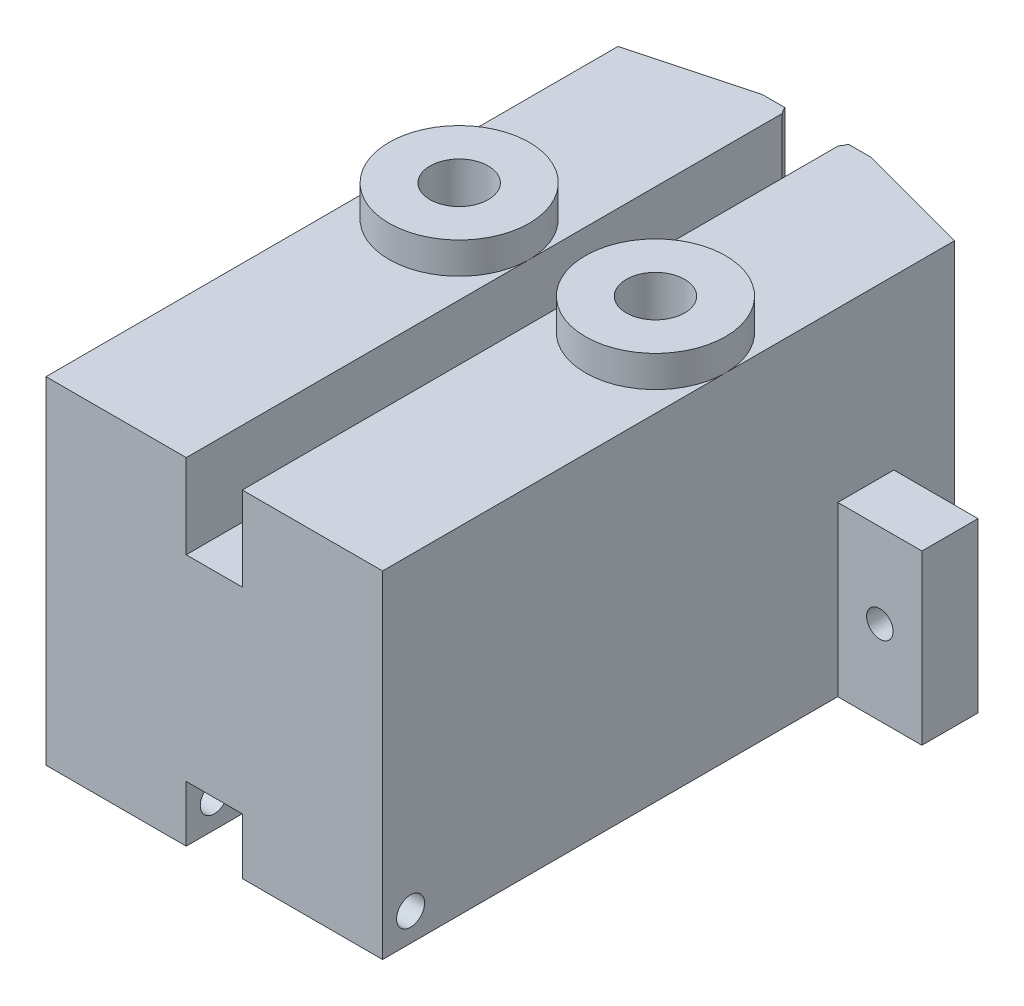
SolidWorks part; units mm, degrees
material "A-Glass Fiber"
ref_plane "Front Plane" through (0, 0, 0) normal (0, 0, 1) x (1, 0, 0)
ref_plane "Top Plane" through (0, 0, 0) normal (0, 1, 0) x (1, 0, 0)
ref_plane "Right Plane" through (0, 0, 0) normal (1, 0, 0) x (0, 0, -1)
sketch "Sketch1" plane through (0, 0, 0) normal (1, 0, 0) x (0, 0, -1)
  line L0 (-19.05, 0) -> (19.05, 0) construction
  line L1 (-19.05, 9.525) -> (19.05, 9.525)
  line L2 (-19.05, 9.525) -> (-19.05, -9.525)
  line L3 (-19.05, -9.525) -> (19.05, -9.525)
  line L4 (19.05, 9.525) -> (19.05, -9.525)
  dimension "D1" = 9.525
  dimension "D2" = 19.05
  dimension "D3" = 38.1
extrude "Boss-Extrude1" add sketch "Sketch1" along normal mid plane 19.05
sketch "Sketch2" plane through (0, 0, 0) normal (0, 1, 0) x (1, 0, 0)
  line L0 (-3.0668, 15.0532) -> (-9.525, 13.3228)
  line L1 (-9.525, 19.05) -> (-9.525, -19.05) construction
  line L2 (3.0668, 15.0532) -> (9.525, 13.3228)
  line L3 (9.525, 19.05) -> (9.525, -19.05) construction
  line L4 (9.525, 19.05) -> (-9.525, 19.05) construction
  arc A0 (-3.0668, 15.0532) -> (3.0668, 15.0532) centre (0, 15.875) cw
  dimension "D1" = 3.175
  dimension "D2" = 15
  dimension "D3" = 15
extrude "Cut-Extrude1" cut sketch "Sketch2" against normal through all both and the other way through all
sketch "Sketch3" plane through (0, 0, 0) normal (0, 1, 0) x (1, 0, 0)
  circle A0 centre (0, 15.875) radius 1.9844
  arc A1 (3.0668, 15.0532) -> (-3.0668, 15.0532) centre (0, 15.875) ccw construction
  dimension "D1" = 3.9688
extrude "Cut-Extrude2" cut sketch "Sketch3" against normal through all both and the other way through all
sketch "Sketch4" plane through (0, 0, 0) normal (0, 0, 1) x (1, 0, 0)
  line L0 (9.525, 9.525) -> (-9.525, 9.525) construction
  line L1 (-1.5875, 9.525) -> (1.5875, 9.525)
  line L2 (-1.5875, 9.525) -> (-1.5875, 4.7625)
  line L3 (-1.5875, 4.7625) -> (1.5875, 4.7625)
  line L4 (1.5875, 9.525) -> (1.5875, 4.7625)
  line L5 (0, -9.525) -> (0, 9.525) construction
  line L6 (9.525, -9.525) -> (-9.525, -9.525) construction
  line L8 (-1.5875, -9.525) -> (1.5875, -9.525)
  line L9 (-1.5875, -9.525) -> (-1.5875, -6.35)
  line L10 (-1.5875, -6.35) -> (1.5875, -6.35)
  line L11 (1.5875, -9.525) -> (1.5875, -6.35)
  dimension "D1" = 4.7625
  dimension "D2" = 3.175
  dimension "D3" = 6.35
extrude "Cut-Extrude3" cut sketch "Sketch4" against normal through all both and the other way through all
sketch "Sketch11" plane through (0, 4.7625, 0) normal (0, 1, 0) x (1, 0, 0)
  circle A0 centre (0, 15.875) radius 3.683
  arc A1 (1.5875, 18.6246) -> (-1.5875, 18.6246) centre (0, 15.875) ccw construction
  dimension "D1" = 0.508
extrude "Cut-Extrude9" cut sketch "Sketch11" against normal offset from surface (6.35 mm away) 2.3813 from offset 2.3813 up to face at (0, -6.35, 2.3813) offset against normal yes
ref_plane "SymmetryPlane" through (0, -0.7937, 0) normal (0, -1, 0) x (-1, 0, 0)
sketch "Sketch12" plane through (0, 0, 0) normal (1, 0, 0) x (0, 0, -1)
  line L0 (18.6246, -6.35) -> (19.05, -6.35) construction
  line L1 (18.6246, -9.525) -> (12.2746, -9.525)
  line L2 (18.6246, -9.525) -> (18.6246, -6.35)
  line L3 (18.6246, -6.35) -> (12.2746, -6.35)
  line L4 (12.2746, -9.525) -> (12.2746, -6.35)
  dimension "D1" = 6.35
extrude "Cut-Extrude10" cut sketch "Sketch12" against normal through all both and the other way through all
sketch "Sketch14" plane through (0, 0, 0) normal (1, 0, 0) x (0, 0, -1)
  line L0 (15.0532, -6.35) -> (19.05, -6.35) construction
  line L1 (12.2746, -9.525) -> (12.2746, -6.35) construction
  line L3 (-19.05, 9.525) -> (-19.05, -9.525) construction
  circle A0 centre (-17.4625, -7.9375) radius 0.7937
  circle A1 centre (10.6871, -7.9375) radius 0.7937
  dimension "D1" = 1.5875
  dimension "D2" = 1.5875
  dimension "D3" = 0.7937
  dimension "D4" = 1.5875
  dimension "D5" = 1.5875
extrude "Cut-Extrude11" cut sketch "Sketch14" against normal through all both and the other way through all
sketch "Sketch15" plane through (0, 9.525, 0) normal (0, 1, 0) x (1, 0, 0)
  line L0 (-9.525, 13.3228) -> (-3.0668, 15.0532)
  line L1 (-3.0668, 15.0532) -> (3.0668, 15.0532)
  line L2 (3.0668, 15.0532) -> (9.525, 13.3228)
  line L3 (9.525, 13.3228) -> (9.525, 19.05)
  line L4 (9.525, 19.05) -> (-9.525, 19.05)
  line L5 (-9.525, 19.05) -> (-9.525, 13.3228)
  arc A0 (1.5875, 18.6246) -> (-1.5875, 18.6246) centre (0, 15.875) ccw construction
extrude "Cut-Extrude12" cut sketch "Sketch15" against normal up to surface (4.7625 mm away) up to face at (0, 4.7625, -18.1499)
sketch "Sketch16" plane through (9.525, 0, 0) normal (1, 0, 0) x (0, 0, -1)
  line L0 (-19.05, -9.525) -> (12.2746, -9.525) construction
  line L1 (9.8934, -9.525) -> (6.7184, -9.525)
  line L2 (9.8934, -9.525) -> (9.8934, 0)
  line L3 (9.8934, 0) -> (6.7184, 0)
  line L4 (6.7184, -9.525) -> (6.7184, 0)
  circle A0 centre (10.6871, -7.9375) radius 0.7937 construction
  dimension "D1" = 3.175
extrude "Boss-Extrude2" add sketch "Sketch16" along normal blind 4.7625
sketch "Sketch17" plane through (-9.525, 0, 0) normal (-1, 0, 0) x (0, 0, 1)
  line L0 (19.05, -9.525) -> (-12.2746, -9.525) construction
  line L1 (-9.8934, -9.525) -> (-6.7184, -9.525)
  line L2 (-9.8934, -9.525) -> (-9.8934, 0)
  line L3 (-9.8934, 0) -> (-6.7184, 0)
  line L4 (-6.7184, -9.525) -> (-6.7184, 0)
  circle A0 centre (-10.6871, -7.9375) radius 0.7937 construction
  dimension "D1" = 3.175
extrude "Boss-Extrude3" add sketch "Sketch17" along normal blind 4.7625
sketch "Sketch18" plane through (0, 0, -9.8934) normal (0, 0, -1) x (-1, 0, 0)
  line L0 (-11.9062, 0) -> (-11.9062, -9.525) construction
  line L1 (-14.2875, 0) -> (-9.525, 0) construction
  line L2 (-14.2875, -9.525) -> (-9.525, -9.525) construction
  line L3 (11.9062, 0) -> (11.9062, -9.525) construction
  line L4 (14.2875, 0) -> (9.525, 0) construction
  line L5 (14.2875, -9.525) -> (9.525, -9.525) construction
  circle A0 centre (-11.9062, -4.7625) radius 0.7493
  circle A1 centre (11.9062, -4.7625) radius 0.7493
  dimension "D2" = 1.4986
  dimension "D3" = 1.4986
  dimension "D1" = 4.7625
extrude "Cut-Extrude13" cut sketch "Sketch18" against normal through all
sketch "Sketch19" plane through (0, 9.525, 0) normal (0, 1, 0) x (1, 0, 0)
  line L0 (0, 19.05) -> (0, -19.05) construction
  line L1 (-1.5875, -19.05) -> (1.5875, -19.05) construction
  line L4 (-1.5875, 14.6844) -> (-1.5875, -19.05) construction
  line L5 (1.5875, 14.6844) -> (1.5875, -19.05) construction
  line L6 (9.525, 13.3228) -> (9.525, -19.05) construction
  line L7 (-14.2875, 6.7184) -> (-9.525, 6.7184) construction
  circle A0 centre (-5.5562, 0.3684) radius 3.9688
  circle A1 centre (5.5563, 0.3684) radius 3.9687
  arc A2 (3.0668, 15.0532) -> (-3.0668, 15.0532) centre (0, 15.875) ccw construction
  dimension "D1" = 6.35
extrude "Boss-Extrude4" add sketch "Sketch19" along normal blind 1.778
sketch "Sketch20" plane through (0, 11.303, 0) normal (0, 1, 0) x (1, 0, 0)
  circle A0 centre (-5.5562, 0.3684) radius 1.651
  circle A1 centre (5.5563, 0.3684) radius 1.651
  dimension "D1" = 3.302
  dimension "D2" = 3.302
extrude "Cut-Extrude14" cut sketch "Sketch20" against normal through all
ref_axis "Axis1" through (11.9063, -4.7625, 27.3814) along (0, 0, -1)
ref_axis "Axis2" through (-11.9062, -4.7625, 27.3841) along (0, 0, -1)
sketch "Sketch21" plane through (0, 0, 19.05) normal (0, 0, 1) x (1, 0, 0)
  point P0 (0, 9.525)
  point P1 (0, -9.525)
  point P2 (0, 7.525)
  point P3 (0, -7.525)
  dimension "D1" = 2
  dimension "D2" = 2
ref_axis "Axis4" through (0, -7.525, 19.05) along (0, 0, 1)
ref_axis "Axis5" through (0, 7.525, 19.529) along (0, 0, 1)
